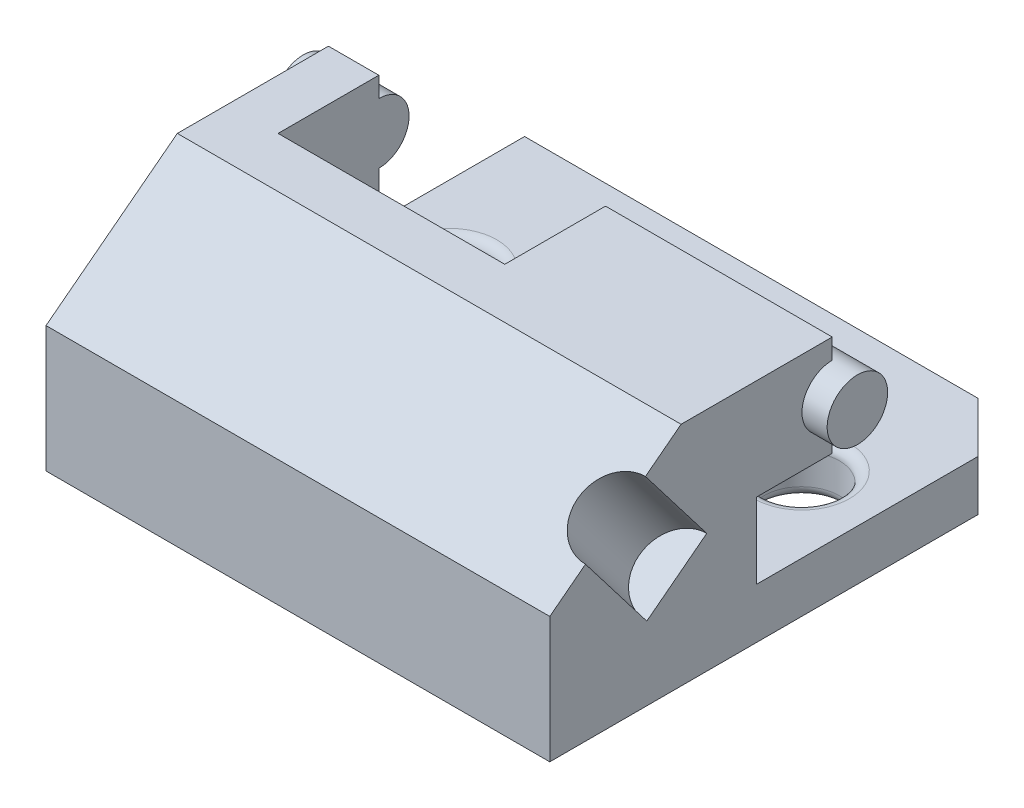
SolidWorks part; units mm, degrees
material "1060 合金"
ref_plane "前视基准面" through (0, 0, 0) normal (0, 0, 1) x (1, 0, 0)
ref_plane "上视基准面" through (0, 0, 0) normal (0, 1, 0) x (1, 0, 0)
ref_plane "右视基准面" through (0, 0, 0) normal (1, 0, 0) x (0, 0, -1)
sketch "草图1" plane through (0, 0, 0) normal (1, 0, 0) x (0, 0, -1)
  line L0 (0, 125.8094) -> (0, -117.1398) construction
  line L1 (-185.2687, 0) -> (195.1683, 0) construction
  line L2 (0, 0) -> (95, 0)
  line L3 (95, 0) -> (95, 10)
  line L4 (95, 10) -> (41.0645, 10)
  line L5 (41.0645, 10) -> (41.0645, 25)
  line L6 (41.0645, 25) -> (56.0645, 25)
  line L7 (56.0645, 25) -> (56.0645, 45)
  line L8 (56.0645, 45) -> (26.0645, 45)
  line L9 (26.0645, 45) -> (0, 25)
  line L10 (0, 25) -> (0, 0)
  dimension "D1" = 95
  dimension "D2" = 25
  dimension "D3" = 20
  dimension "D4" = 52.5
  dimension "D5" = 30
  dimension "D6" = 15
  dimension "D7" = 20
  dimension "D8" = 15
extrude "凸台-拉伸1" add sketch "草图1" along normal blind 100
sketch "草图2" plane through (100, 0, 0) normal (1, 0, 0) x (0, 0, -1)
  line L0 (56.0645, 25) -> (56.0645, 45) construction
  line L1 (56.0645, 45) -> (26.0645, 45) construction
  circle A0 centre (56.0645, 35) radius 6
  dimension "D1" = 12
  dimension "D2" = 10
extrude "凸台-拉伸2" add sketch "草图2" against normal offset from surface (105 mm away) 5 up to face at (0, 20.5556, -45.5914) offset beyond the face yes
extrude "凸台-拉伸3" add sketch "草图2<2>" along normal offset from surface (5 mm away) 5 up to face at (100, 23.1818, -48.0411) offset beyond the face yes
sketch "草图2<2>" plane through (100, 0, 0) normal (1, 0, 0) x (0, 0, -1) same geometry as "草图2"
sketch "草图4" plane through (0, 45, 0) normal (0, 1, 0) x (1, 0, 0)
  line L0 (0, 56.0645) -> (0, 26.0645) construction
  line L1 (10, 62.0645) -> (55, 62.0645)
  line L2 (10, 62.0645) -> (10, 36.0645)
  line L3 (10, 36.0645) -> (55, 36.0645)
  line L4 (55, 62.0645) -> (55, 36.0645)
  line L5 (100, 26.0645) -> (0, 26.0645) construction
  line L6 (105, 62.0645) -> (-5, 62.0645) construction
  dimension "D1" = 45
  dimension "D2" = 10
  dimension "D3" = 10
extrude "切除-拉伸1" cut sketch "草图4" against normal up to surface (35 mm away) up to face at (50, 10, -68.0323)
sketch "草图6" plane through (0, 15.7352, 12.0741) normal (0, 0.7934, 0.6088) x (1, 0, 0)
  line L0 (100, 48.0726) -> (100, 15.219) construction
  circle A0 centre (100, 31.6458) radius 7.5
  dimension "D1" = 15
extrude "切除-拉伸4" cut sketch "草图6" against normal blind 20
sketch "草图7" plane through (0, 10, 0) normal (0, 1, 0) x (1, 0, 0)
  line L0 (-25.5618, 65) -> (133.8719, 65) construction
  line L1 (35, 65) -> (65, 65) construction
  line L2 (35, 72.5) -> (65, 72.5)
  line L3 (35, 57.5) -> (65, 57.5)
  line L4 (100, 95) -> (0, 95) construction
  line L5 (0, 95) -> (0, 41.0645) construction
  circle A0 centre (15, 65) radius 7.5
  circle A1 centre (85, 65) radius 7.5
  arc A2 (35, 72.5) -> (35, 57.5) centre (35, 65) ccw
  arc A3 (65, 57.5) -> (65, 72.5) centre (65, 65) ccw
  point P8 (50, 65)
  point P19 (18.1304, 65)
  dimension "D1" = 15
  dimension "D2" = 30
  dimension "D3" = 15
  dimension "D4" = 30
  dimension "D5" = 15
  dimension "D6" = 20
  dimension "D7" = 20
extrude "切除-拉伸5" cut sketch "草图7" against normal up to surface (10 mm away) up to face at (50, 0, -47.5)
fillet "圆角1" radius 2 12 edges at (50, 10, -72.5) (72.5, 10, -65) (50, 10, -57.5) (50, 0, -57.5) (72.5, 0, -65) (50, 0, -72.5) (85, 10, -57.5) (85, 0, -57.5) (27.5, 10, -65) (27.5, 0, -65) (15, 10, -57.5) (15, 0, -57.5)
chamfer "倒角1" distance 10 angle 45 1 edges at (100, 5, -95)
